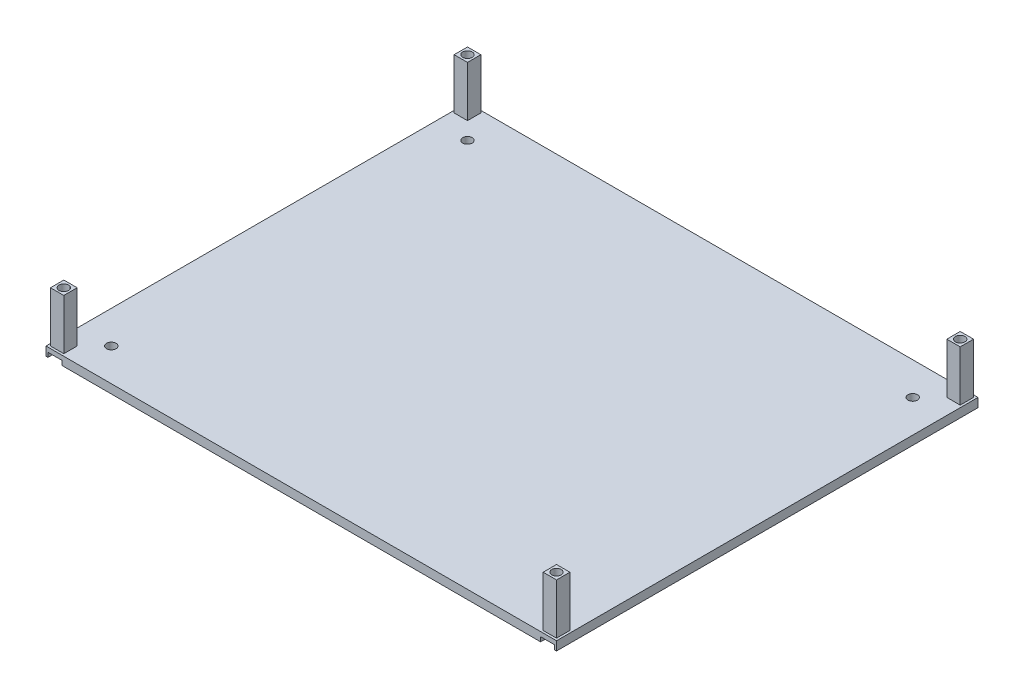
SolidWorks part; units mm, degrees
ref_plane "Front Plane" through (0, 0, 0) normal (0, 0, 1) x (1, 0, 0)
ref_plane "Top Plane" through (0, 0, 0) normal (0, 1, 0) x (1, 0, 0)
ref_plane "Right Plane" through (0, 0, 0) normal (1, 0, 0) x (0, 0, -1)
sketch "Sketch1" plane through (0, 0, 0) normal (0, 1, 0) x (1, 0, 0)
  line L0 (-80, 65) -> (-80, 71)
  line L1 (-80, -65) -> (80, -65)
  line L2 (-80, -65) -> (-80, 65)
  line L3 (-80, 65) -> (80, 65)
  line L4 (80, -65) -> (80, 65)
  line L5 (0, 65) -> (0, -65) construction
  line L6 (-80, 0) -> (80, 0) construction
  line L7 (-86, -71) -> (86, -71)
  line L8 (-86, -71) -> (-86, 71)
  line L9 (-86, 71) -> (86, 71)
  line L10 (86, -71) -> (86, 71)
  line L11 (0, 71) -> (0, -71) construction
  line L12 (-86, 0) -> (86, 0) construction
  line L13 (-80, 65) -> (-86, 65)
  line L14 (-86, 71) -> (-80, 65) construction
  line L15 (-85.35, 70.35) -> (-85.35, 71)
  line L16 (-80.75, 65.75) -> (-85.25, 65.75)
  line L17 (-80.75, 65.75) -> (-80.75, 70.25)
  line L18 (-80.75, 70.25) -> (-85.25, 70.25)
  line L19 (-85.25, 65.75) -> (-85.25, 70.25)
  line L20 (-83, 70.25) -> (-83, 65.75) construction
  line L21 (-80.75, 68) -> (-85.25, 68) construction
  line L22 (-85.35, 65.65) -> (-80.65, 65.65)
  line L23 (-85.35, 65.65) -> (-85.35, 70.35)
  line L24 (-85.35, 70.35) -> (-80.65, 70.35)
  line L25 (-80.65, 65.65) -> (-80.65, 70.35)
  line L26 (-83, 70.35) -> (-83, 65.65) construction
  line L27 (-85.35, 68) -> (-80.65, 68) construction
  line L28 (-80.65, 70.35) -> (-80.65, 71)
  line L29 (80.65, 65.65) -> (80.65, 70.35)
  line L30 (85.35, 70.35) -> (80.65, 70.35)
  line L31 (85.35, 65.65) -> (85.35, 70.35)
  line L32 (85.35, 65.65) -> (80.65, 65.65)
  line L33 (80.75, 70.25) -> (85.25, 70.25)
  line L34 (85.25, 65.75) -> (85.25, 70.25)
  line L35 (80.75, 65.75) -> (85.25, 65.75)
  line L36 (80.75, 65.75) -> (80.75, 70.25)
  line L37 (80.65, 70.35) -> (80.65, 71)
  line L38 (85.35, 70.35) -> (85.35, 71)
  line L39 (85.35, -65.65) -> (80.65, -65.65)
  line L40 (85.35, -65.65) -> (85.35, -70.35)
  line L41 (80.65, -65.65) -> (80.65, -70.35)
  line L42 (85.35, -70.35) -> (80.65, -70.35)
  line L43 (80.75, -65.75) -> (80.75, -70.25)
  line L44 (80.75, -65.75) -> (85.25, -65.75)
  line L45 (85.25, -65.75) -> (85.25, -70.25)
  line L46 (80.75, -70.25) -> (85.25, -70.25)
  line L47 (85.35, -70.35) -> (85.35, -71)
  line L48 (80.65, -70.35) -> (80.65, -71)
  line L49 (-85.35, -65.65) -> (-85.35, -70.35)
  line L50 (-85.35, -65.65) -> (-80.65, -65.65)
  line L51 (-80.65, -65.65) -> (-80.65, -70.35)
  line L52 (-85.35, -70.35) -> (-80.65, -70.35)
  line L53 (-80.75, -70.25) -> (-85.25, -70.25)
  line L54 (-85.25, -65.75) -> (-85.25, -70.25)
  line L55 (-80.75, -65.75) -> (-85.25, -65.75)
  line L56 (-80.75, -65.75) -> (-80.75, -70.25)
  line L57 (-80.65, -70.35) -> (-80.65, -71)
  line L58 (-85.35, -70.35) -> (-85.35, -71)
  circle A0 centre (-75, 60) radius 1.6
  circle A1 centre (75, 60) radius 1.6
  circle A2 centre (75, -60) radius 1.6
  circle A3 centre (-75, -60) radius 1.6
  circle A4 centre (-83, 68) radius 1.6
  circle A5 centre (83, 68) radius 1.6
  circle A6 centre (83, -68) radius 1.6
  circle A7 centre (-83, -68) radius 1.6
  point P0 (0, 0)
  point P4 (0, 0)
  dimension "D5" = 3.2
  dimension "D8" = 3.2
  dimension "D1" = 160
  dimension "D2" = 130
  dimension "D3" = 6
  dimension "D4" = 6
  dimension "D6" = 5
  dimension "D7" = 5
  dimension "D9" = 4.5
  dimension "D10" = 0.1
  dimension "D11" = 0.1
extrude "Boss-Extrude1" add sketch "Sketch1" along normal blind 3 contours L2 L8 | L1 L4 L3 L2 A1 A0 A2 A3 | L3 L9 L23 | L4 L10 | L1 L31 L7 | L3 L23 L9 | L2 L8 | L4 L10 | L3 L9 | L4 L10 | L1 L7 | L1 L7 L31 | L2 L8 | L42 L40 L39 L41 L46 L43 L44 L45 | A5 | L8 L7 L10 L9 | A7 | A6 | A4 | A3 | A2 | A1 | A0 region at (-83, 0, -65.0849) region at (0, 0, 0) region at (-77.7696, 0, -68) region at (80.7165, 0, 68) region at (83, 0, -68)
extrude "Boss-Extrude2" add sketch "Sketch1<3>" along normal blind 20 contours L56 L55 L54 L53 A7 | L43 L46 L45 L44 A6 | L36 L35 L34 L33 A5 | L19 L16 L17 L18 A4 region at (-83, 0, -65.8136) region at (83, 0, -70.1864) region at (83, 0, 65.8136) region at (-83, 0, 70.1864)
sketch "Sketch1<3>" plane through (0, 0, 0) normal (0, 1, 0) x (1, 0, 0) same geometry as "Sketch1"
extrude "Cut-Extrude1" cut sketch "Sketch1<5>" along normal blind 1.5 contours L36 L35 L34 L33 A5 | L30 L38 L9 L37 | L32 L31 L30 L29 L35 L36 L33 L34 | L19 L16 L17 L18 A4 | L22 L25 L24 L23 L16 L19 L18 L17 | L24 L28 L9 L15 | L56 L55 L54 L53 A7 | L49 L52 L51 L50 L55 L56 L53 L54 | L52 L58 L7 L57 | L43 L46 L45 L44 A6 | L42 L48 L7 L47 | L42 L40 L39 L41 L46 L43 L44 L45 region at (-83, 0, -70.675) region at (83, 0, -70.675) region at (-80.7165, 0, -68) region at (83, 0, -70.2835) region at (-83, 0, 70.675) region at (-85.2835, 0, 68) region at (83, 0, 70.675) region at (80.7165, 0, 68) region at (-83, 0, -65.8136) region at (83, 0, -70.1864) region at (83, 0, 65.8136) region at (-83, 0, 70.1864)
sketch "Sketch1<5>" plane through (0, 0, 0) normal (0, 1, 0) x (1, 0, 0) same geometry as "Sketch1"
